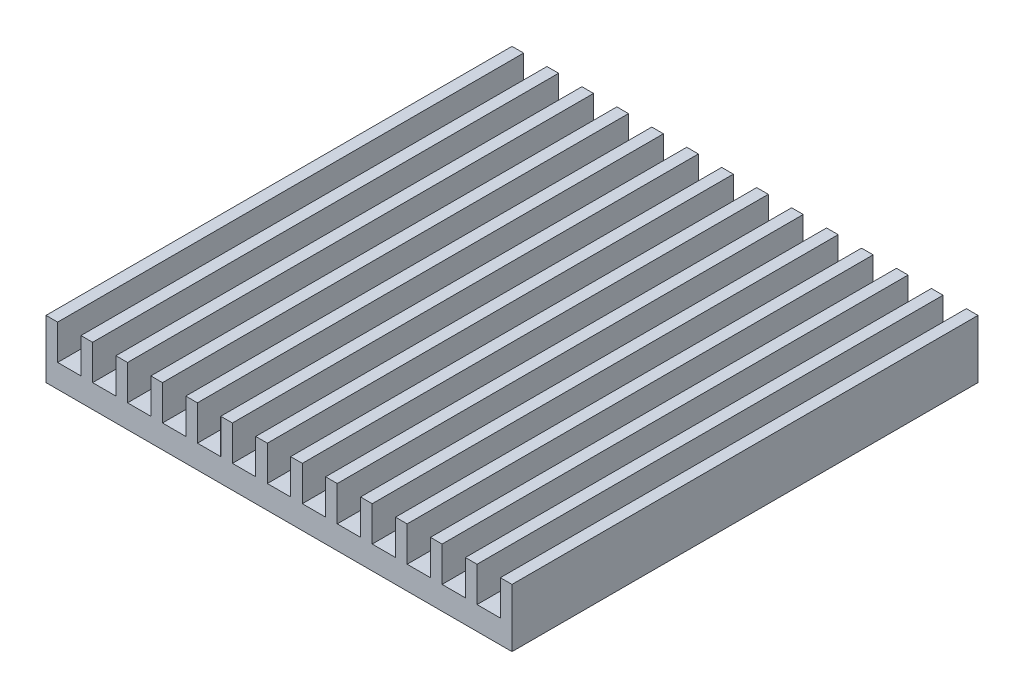
SolidWorks part; units mm, degrees
ref_plane "前视基准面" through (0, 0, 0) normal (0, 0, 1) x (1, 0, 0)
ref_plane "上视基准面" through (0, 0, 0) normal (0, 1, 0) x (1, 0, 0)
ref_plane "右视基准面" through (0, 0, 0) normal (1, 0, 0) x (0, 0, -1)
other "Configuration Table"
sketch "草图1" plane through (0, 0, 0) normal (0, 1, 0) x (1, 0, 0)
  line L1 (-20, 20) -> (20, 20)
  line L2 (-20, 20) -> (-20, -20)
  line L3 (-20, -20) -> (20, -20)
  line L4 (20, 20) -> (20, -20)
  line L5 (-20, 20) -> (20, -20) construction
  line L6 (-20, -20) -> (20, 20) construction
  point P0 (0, 0)
  dimension "D1" = 40
  dimension "D2" = 40
extrude "凸台-拉伸1" add sketch "草图1" along normal blind 2
sketch "草图2" plane through (0, 2, 0) normal (0, 1, 0) x (1, 0, 0)
  line L0 (-20, -20) -> (20, -20) construction
  line L1 (-20, 20) -> (-19, 20)
  line L2 (-20, 20) -> (-20, -20)
  line L3 (-20, -20) -> (-19, -20)
  line L4 (-19, 20) -> (-19, -20)
  line L5 (-17, 20) -> (-16, 20)
  line L6 (-17, 20) -> (-17, -20)
  line L7 (-17, -20) -> (-16, -20)
  line L8 (-16, 20) -> (-16, -20)
  line L9 (-14, 20) -> (-13, 20)
  line L10 (-14, 20) -> (-14, -20)
  line L11 (-14, -20) -> (-13, -20)
  line L12 (-13, 20) -> (-13, -20)
  line L13 (-11, 20) -> (-10, 20)
  line L14 (-11, 20) -> (-11, -20)
  line L15 (-11, -20) -> (-10, -20)
  line L16 (-10, 20) -> (-10, -20)
  line L17 (-8, 20) -> (-7, 20)
  line L18 (-8, 20) -> (-8, -20)
  line L19 (-8, -20) -> (-7, -20)
  line L20 (-7, 20) -> (-7, -20)
  line L21 (-5, 20) -> (-4, 20)
  line L22 (-5, 20) -> (-5, -20)
  line L23 (-5, -20) -> (-4, -20)
  line L24 (-4, 20) -> (-4, -20)
  line L25 (-2, 20) -> (-1, 20)
  line L26 (-2, 20) -> (-2, -20)
  line L27 (-2, -20) -> (-1, -20)
  line L28 (-1, 20) -> (-1, -20)
  line L29 (1, 20) -> (2, 20)
  line L30 (1, 20) -> (1, -20)
  line L31 (1, -20) -> (2, -20)
  line L32 (2, 20) -> (2, -20)
  line L33 (4, 20) -> (5, 20)
  line L34 (4, 20) -> (4, -20)
  line L35 (4, -20) -> (5, -20)
  line L36 (5, 20) -> (5, -20)
  line L37 (7, 20) -> (8, 20)
  line L38 (7, 20) -> (7, -20)
  line L39 (7, -20) -> (8, -20)
  line L40 (8, 20) -> (8, -20)
  line L41 (10, 20) -> (11, 20)
  line L42 (10, 20) -> (10, -20)
  line L43 (10, -20) -> (11, -20)
  line L44 (11, 20) -> (11, -20)
  line L45 (13, 20) -> (14, 20)
  line L46 (13, 20) -> (13, -20)
  line L47 (13, -20) -> (14, -20)
  line L48 (14, 20) -> (14, -20)
  line L49 (16, 20) -> (17, 20)
  line L50 (16, 20) -> (16, -20)
  line L51 (16, -20) -> (17, -20)
  line L52 (17, 20) -> (17, -20)
  line L53 (19, 20) -> (20, 20)
  line L54 (19, 20) -> (19, -20)
  line L55 (19, -20) -> (20, -20)
  line L56 (20, 20) -> (20, -20)
  dimension "D1" = 1
  dimension "D2" = 14
extrude "凸台-拉伸2" add sketch "草图2" along normal blind 3
